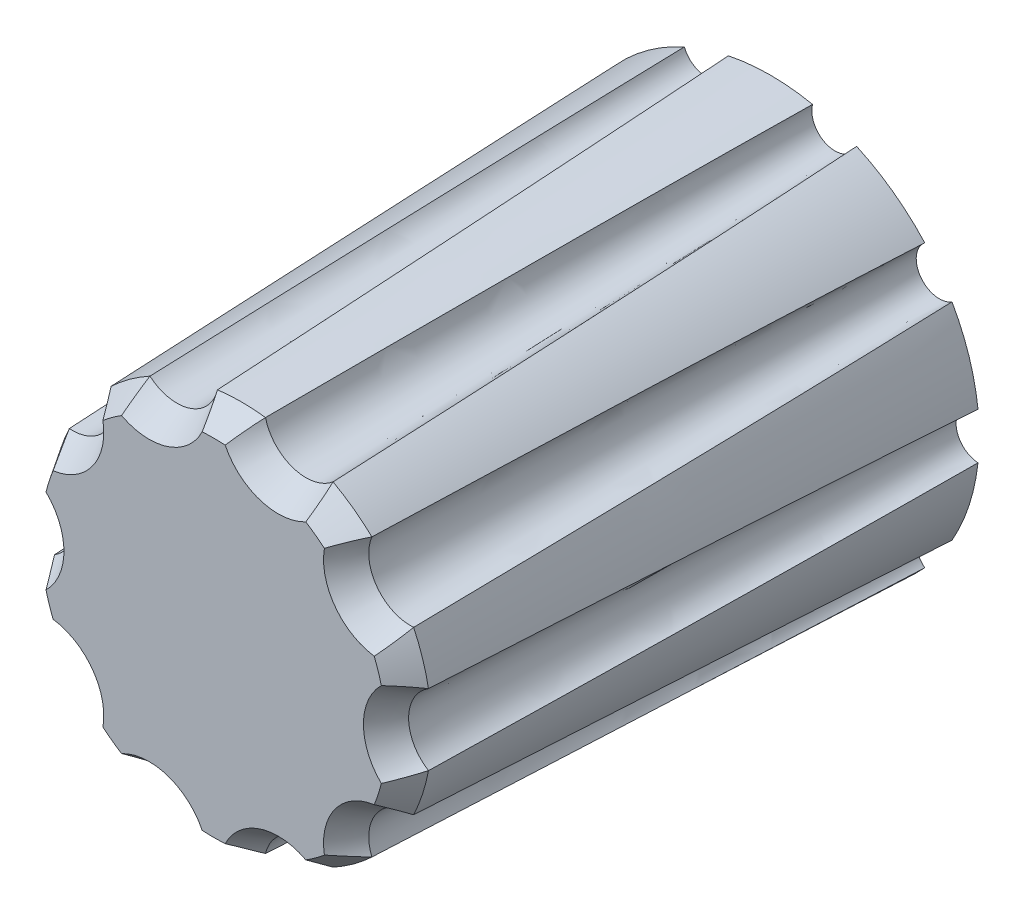
SolidWorks part; units mm, degrees
ref_plane "Plan de face" through (0, 0, 0) normal (0, 0, 1) x (1, 0, 0)
ref_plane "Plan de dessus" through (0, 0, 0) normal (0, 1, 0) x (1, 0, 0)
ref_plane "Plan de droite" through (0, 0, 0) normal (1, 0, 0) x (0, 0, -1)
sketch "Esquisse1" plane through (0, 0, 0) normal (0, 0, 1) x (1, 0, 0)
  line L0 (-13.0824, 0) -> (17.5938, 0) construction
  circle A0 centre (0, 0) radius 4.5
  circle A1 centre (-4.5, 0) radius 0.5
  circle A2 centre (-3.6406, 2.645) radius 0.5
  circle A3 centre (-1.3906, 4.2798) radius 0.5
  circle A4 centre (1.3906, 4.2798) radius 0.5
  circle A5 centre (3.6406, 2.645) radius 0.5
  circle A6 centre (4.5, 0) radius 0.5
  circle A7 centre (3.6406, -2.645) radius 0.5
  circle A8 centre (1.3906, -4.2798) radius 0.5
  circle A9 centre (-1.3906, -4.2798) radius 0.5
  circle A10 centre (-3.6406, -2.645) radius 0.5
  point P35 (0, 0)
  dimension "D1" = 9
  dimension "D2" = 1
  dimension "D3" = 10
extrude "Boss.-Extru.1" add sketch "Esquisse1" along normal blind 12 draft 2
chamfer "Chanfrein2" distance 0.6 angle 30 20 edges at (-3.8812, 1.2611, 12) (-2.8971, 2.1048, 12) (-2.3987, 3.3016, 12) (-1.1066, 3.4057, 12) (0, 4.081, 12) (1.1066, 3.4057, 12) (2.3987, 3.3016, 12) (2.8971, 2.1048, 12) (3.8812, 1.2611, 12) (3.581, 0, 12) (3.8812, -1.2611, 12) (2.8971, -2.1048, 12) (2.3987, -3.3016, 12) (1.1066, -3.4057, 12) (0, -4.081, 12) (-1.1066, -3.4057, 12) (-2.3987, -3.3016, 12) (-2.8971, -2.1048, 12) (-3.8812, -1.2611, 12) (-3.581, 0, 12)
sketch "Esquisse2" plane through (0, 0, 0) normal (0, 0, -1) x (-1, 0, 0)
  line L0 (2.6552, -1.6) -> (-2.6552, -1.6)
  circle A0 centre (0, 0) radius 3.1
  dimension "D1" = 6.2
  dimension "D2" = 1.6
extrude "Enlèv. mat.-Extru.1" cut sketch "Esquisse2" against normal blind 10 contours L0 A0
sketch "Esquisse4" plane through (0, 0, 0) normal (0, 0, -1) x (-1, 0, 0)
  line L0 (2.6552, -1.6) -> (-2.6552, -1.6) construction
  circle A0 centre (-2.6552, -1.6) radius 0.2
  circle A1 centre (2.5981, -1.6) radius 0.2
  dimension "D1" = 0.4
  dimension "D2" = 0.4
extrude "Enlèv. mat.-Extru.4" cut sketch "Esquisse4" against normal blind 10
chamfer "Chanfrein3" distance 0.2 angle 45 1 edges at (0.0286, -1.6, 0)
